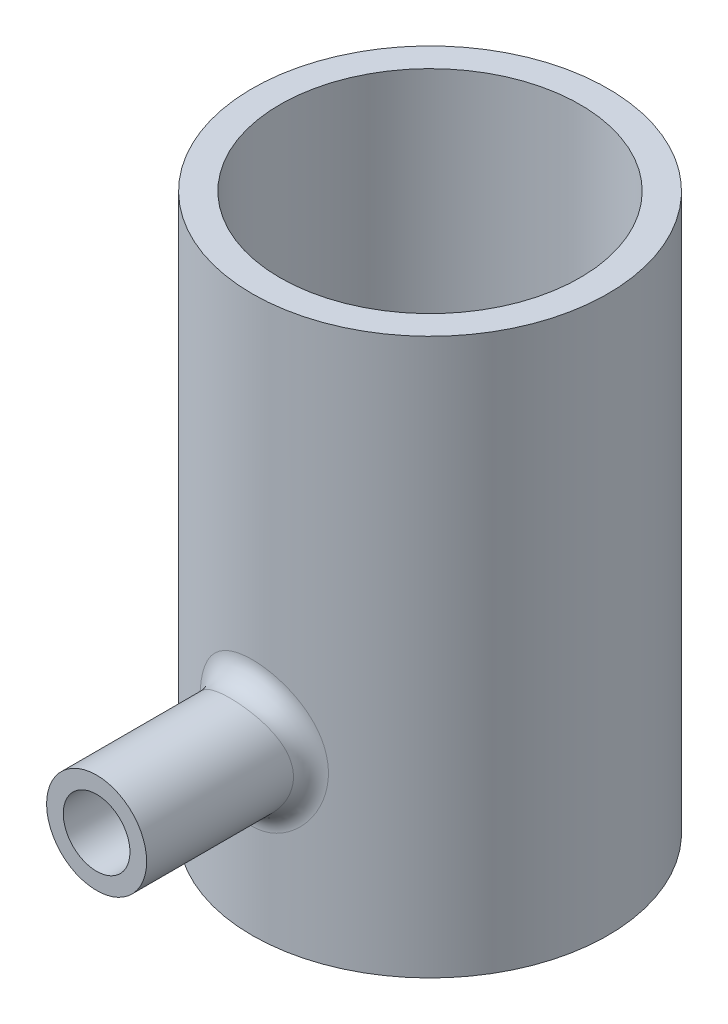
SolidWorks part; units mm, degrees
ref_plane "Front Plane" through (0, 0, 0) normal (0, 0, 1) x (1, 0, 0)
ref_plane "Top Plane" through (0, 0, 0) normal (0, 1, 0) x (1, 0, 0)
ref_plane "Right Plane" through (0, 0, 0) normal (1, 0, 0) x (0, 0, -1)
sketch "Sketch1" plane through (0, 0, 0) normal (0, 1, 0) x (1, 0, 0)
  circle A0 centre (0, 0) radius 32
  circle A1 centre (0, 0) radius 27
  dimension "D1" = 64
  dimension "D2" = 54
extrude "Boss-Extrude1" add sketch "Sketch1" along normal blind 100
sketch "Sketch2" plane through (0, 0, 0) normal (0, 0, 1) x (1, 0, 0)
  circle A0 centre (0, 30) radius 9
  circle A1 centre (0, 30) radius 6
  dimension "D1" = 12
  dimension "D2" = 18
  dimension "D3" = 30
extrude "Boss-Extrude2" add sketch "Sketch2" along normal blind 60
sketch "Sketch3" plane through (0, 100, 0) normal (0, 1, 0) x (1, 0, 0)
  circle A0 centre (0, 0) radius 27
  circle A1 centre (0, 0) radius 27 construction
extrude "Cut-Extrude1" cut sketch "Sketch3" against normal through all
sketch "Sketch4" plane through (0, 0, 60) normal (0, 0, 1) x (1, 0, 0)
  circle A0 centre (0, 30) radius 6
  circle A1 centre (0, 30) radius 6 construction
extrude "Cut-Extrude2" cut sketch "Sketch4" against normal blind 60
fillet "Fillet1" radius 10 1 edges at (-5.8753, 31.217, 26.353)
fillet "Fillet3" radius 4 1 edges at (8.8409, 31.6846, 30.7545)
thread "Thread1" [suppressed] pitch 6 start angle 0, offset 86, length 15, pitch 6, diameter 64
ref_plane "Plane1" through (-32, 14, 0) normal (0, 0, 1) x (-1, 0, 0)
sketch "Thread Profile1" plane through (-32, 14, 0) normal (0, 0, 1) x (-1, 0, 0)
  line L0 (0, 0) -> (0, 6) construction
  line L11 (0, 0) -> (0, 5.25)
  line L12 (0, 5.25) -> (-3.2476, 3.375)
  line L13 (-3.2476, 3.375) -> (-3.2476, 1.875)
  line L15 (-3.2476, 1.875) -> (0, 0)
  line L17 (-3.2476, 2.625) -> (0, 2.625) construction
  point P2 (0, 0)
  dimension "Pitch" = 6
  dimension "Profile_Angle" = 60
  dimension "Profile_Land" = 1.5
  dimension "Profile_Height" = 3.2476
sketch "Sketch14" plane through (0, 100, 0) normal (0, 1, 0) x (1, 0, 0)
chamfer "Chamfer1" [suppressed] distance 0.2 angle 70
